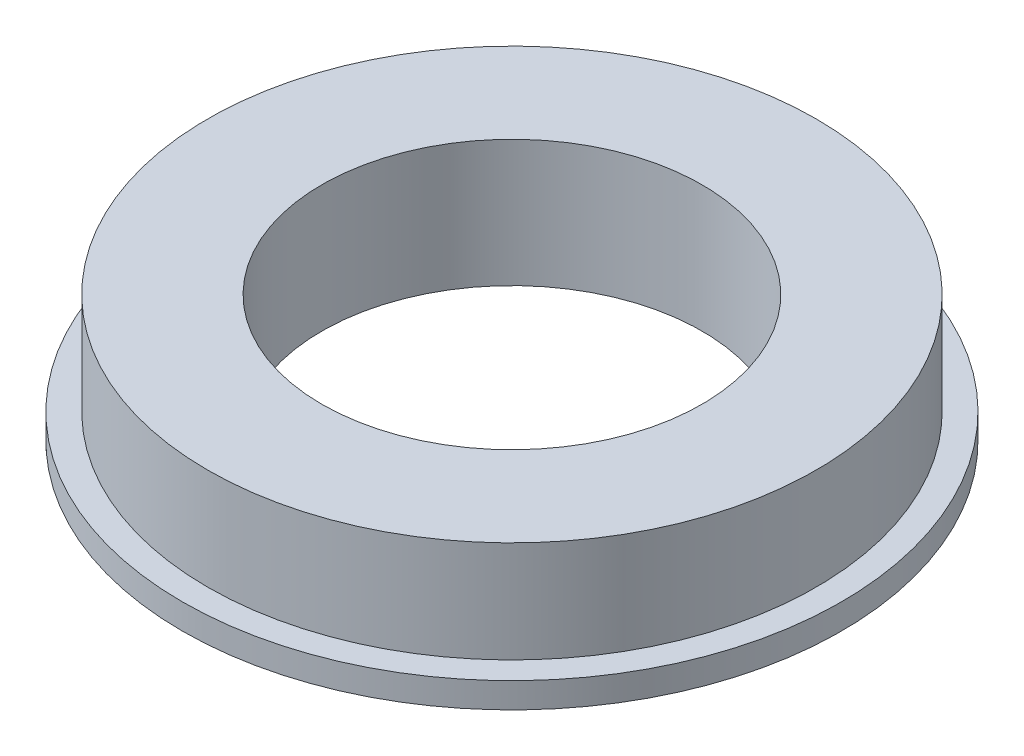
SolidWorks part; units mm, degrees
material "合金钢"
ref_plane "前视基准面" through (0, 0, 0) normal (0, 0, 1) x (1, 0, 0)
ref_plane "上视基准面" through (0, 0, 0) normal (0, 1, 0) x (1, 0, 0)
ref_plane "右视基准面" through (0, 0, 0) normal (1, 0, 0) x (0, 0, -1)
sketch "草图1" plane through (0, 0, 0) normal (0, 1, 0) x (1, 0, 0)
  circle A0 centre (0, 0) radius 7.5
  circle A1 centre (0, 0) radius 12
  circle A2 centre (0, 0) radius 13
  dimension "D1" = 15
  dimension "D2" = 24
  dimension "D3" = 26
extrude "凸台-拉伸1" add sketch "草图1" along normal blind 5 contours A1 A0 region at (-11.6606, 0, 0)
extrude "凸台-拉伸2" add sketch "草图1<3>" along normal blind 1 contours A2 A1 region at (-12.6323, 0, 0)
sketch "草图1<3>" plane through (0, 0, 0) normal (0, 1, 0) x (1, 0, 0) same geometry as "草图1"
